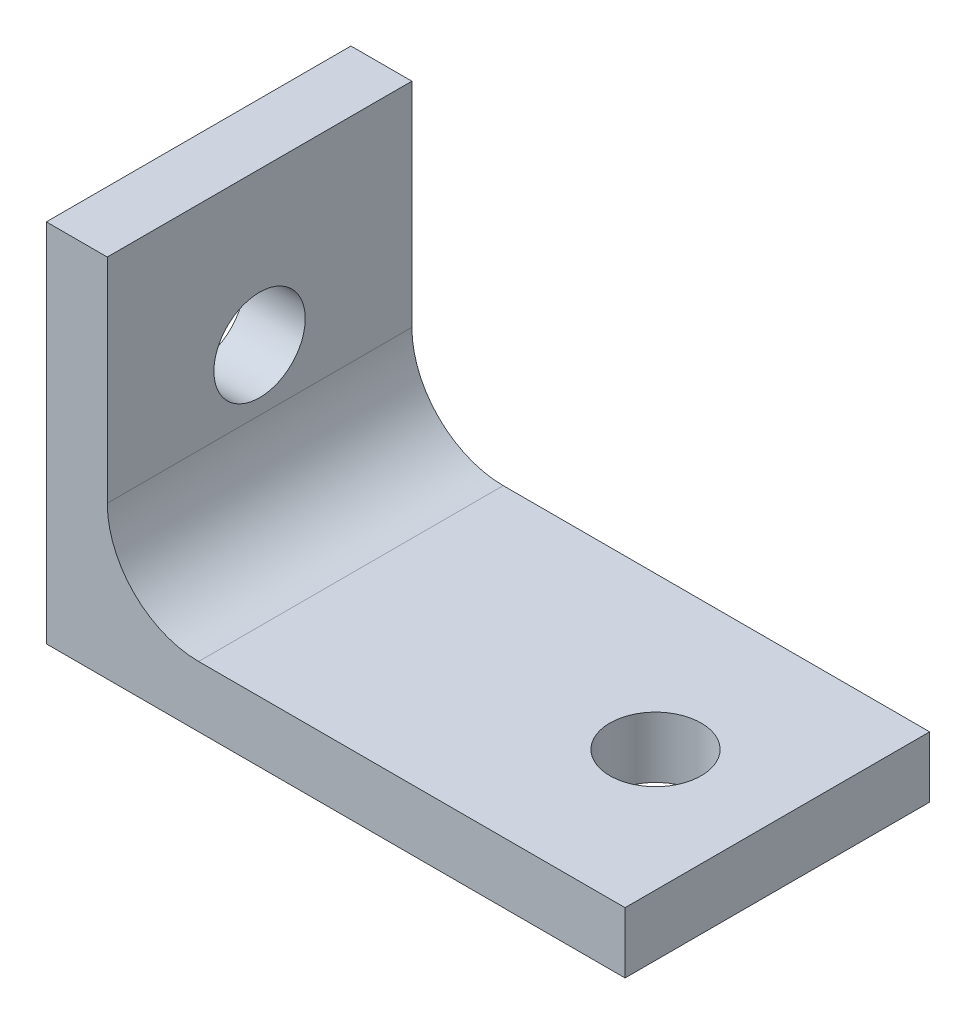
SolidWorks part; units mm, degrees
ref_plane "Front Plane" through (0, 0, 0) normal (0, 0, 1) x (1, 0, 0)
ref_plane "Top Plane" through (0, 0, 0) normal (0, 1, 0) x (1, 0, 0)
ref_plane "Right Plane" through (0, 0, 0) normal (1, 0, 0) x (0, 0, -1)
sketch "Sketch1" plane through (0, 0, 0) normal (0, 0, 1) x (1, 0, 0)
  line L0 (-6.8035, 2.1056) -> (-6.8035, -9.8944)
  line L1 (-6.8035, -9.8944) -> (12.1965, -9.8944)
  line L2 (12.1965, -9.8944) -> (12.1965, -7.8944)
  line L3 (12.1965, -7.8944) -> (-4.8035, -7.8944)
  line L4 (-4.8035, -7.8944) -> (-4.8035, 2.1056)
  line L5 (-4.8035, 2.1056) -> (-6.8035, 2.1056)
  dimension "D1" = 19
  dimension "D2" = 12
  dimension "D3" = 2
  dimension "D4" = 2
extrude "Boss-Extrude1" add sketch "Sketch1" along normal blind 10
sketch "Sketch2" plane through (-4.8035, 0, 0) normal (1, 0, 0) x (0, 0, -1)
  line L0 (-5, 2.1056) -> (-5, -7.8944) construction
  line L1 (-10, 2.1056) -> (0, 2.1056) construction
  line L2 (-10, -7.8944) -> (0, -7.8944) construction
  line L3 (-10, -2.8944) -> (0, -2.8944) construction
  line L4 (-10, -7.8944) -> (-10, 2.1056) construction
  line L5 (0, -7.8944) -> (0, 2.1056) construction
  circle A1 centre (-5, -2.8944) radius 1.5
  dimension "D1" = 3
extrude "Cut-Extrude1" cut sketch "Sketch2" against normal through all
sketch "Sketch3" plane through (0, -7.8944, 0) normal (0, 1, 0) x (1, 0, 0)
  line L0 (-6.8035, -5) -> (8.1965, -5) construction
  line L1 (-6.8035, -10) -> (-6.8035, 0) construction
  circle A0 centre (8.1965, -5) radius 1.5
  dimension "D2" = 3
  dimension "D1" = 15
extrude "Cut-Extrude2" cut sketch "Sketch3" against normal through all
fillet "Fillet1" radius 3 1 edges at (-4.8035, -7.8944, 5)
